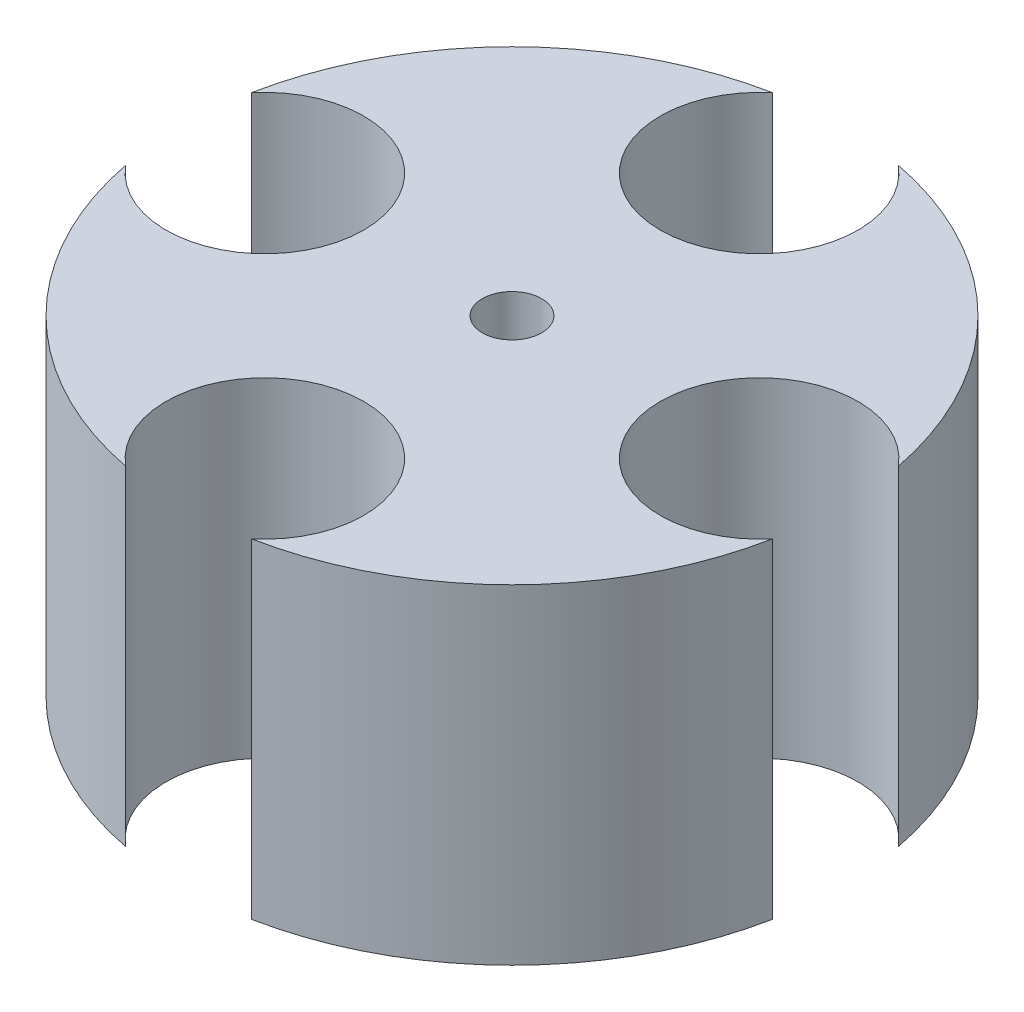
SolidWorks part; units mm, degrees
ref_plane "Front Plane" through (0, 0, 0) normal (0, 0, 1) x (1, 0, 0)
ref_plane "Top Plane" through (0, 0, 0) normal (0, 1, 0) x (1, 0, 0)
ref_plane "Right Plane" through (0, 0, 0) normal (1, 0, 0) x (0, 0, -1)
sketch "Sketch1" plane through (0, 0, 0) normal (0, 1, 0) x (1, 0, 0)
  circle A0 centre (0, 0) radius 50.8
extrude "Boss-Extrude1" add sketch "Sketch1" along normal blind 50.8
sketch "Sketch2" plane through (0, 50.8, 0) normal (0, 1, 0) x (1, 0, 0)
  circle A0 centre (0, 0) radius 38.1
  circle A1 centre (0, 38.1) radius 15.24
  circle A2 centre (-38.1, 0) radius 15.24
  circle A3 centre (0, -38.1) radius 15.24
  circle A4 centre (38.1, 0) radius 15.24
extrude "Cut-Extrude1" cut sketch "Sketch2" against normal blind 50.8 contours A4 | A1 | A2 | A3
sketch "Sketch3" plane through (0, 50.8, 0) normal (0, 1, 0) x (1, 0, 0)
  circle A0 centre (0, 0) radius 4.5722
extrude "Cut-Extrude2" cut sketch "Sketch3" against normal through all
